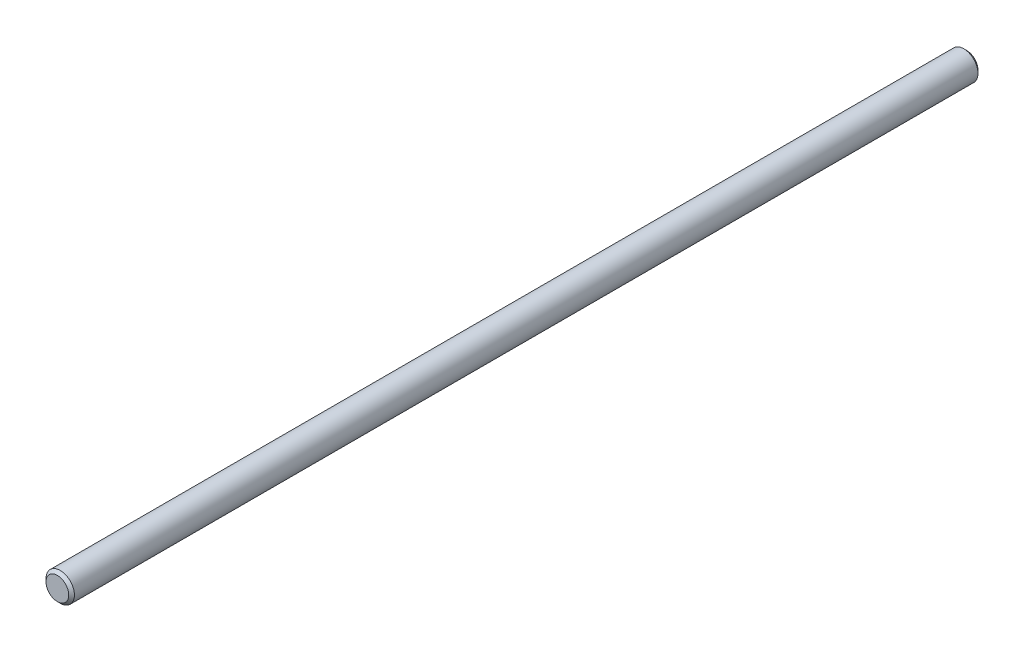
SolidWorks part; units mm, degrees
ref_plane "Front" through (0, 0, 0) normal (0, 0, 1) x (1, 0, 0)
ref_plane "Top" through (0, 0, 0) normal (0, 1, 0) x (1, 0, 0)
ref_plane "Right" through (0, 0, 0) normal (1, 0, 0) x (0, 0, -1)
sketch "Sketch1" plane through (0, 0, 0) normal (0, 0, 1) x (1, 0, 0)
  circle A0 centre (0, 0) radius 4.7625
  dimension "dia" = 9.525
extrude "Extrude1" add sketch "Sketch1" along normal mid plane 304.8
sketch "Sketch2" plane through (0, 0, 0) normal (1, 0, 0) x (0, 0, -1)
  point P0 (-152.4, 4.7625)
  point P1 (152.4, 4.7625)
chamfer "Chamfer1" distance 0.9525 angle 45 2 edges at (4.7625, 0, -152.4) (4.7625, 0, 152.4)
equation "\"D1@Chamfer1\" = \"dia@Sketch1\" * .1"
